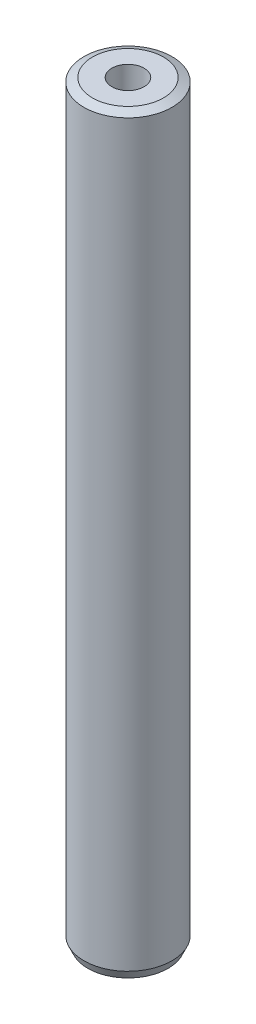
SolidWorks part; units mm, degrees
ref_plane "Front Plane" through (0, 0, 0) normal (0, 0, 1) x (1, 0, 0)
ref_plane "Top Plane" through (0, 0, 0) normal (0, 1, 0) x (1, 0, 0)
ref_plane "Right Plane" through (0, 0, 0) normal (1, 0, 0) x (0, 0, -1)
sketch "Sketch1" plane through (0, 0, 0) normal (0, 1, 0) x (1, 0, 0)
  circle A0 centre (0, 0) radius 15
  dimension "SHAFT_OD" = 30
extrude "Boss-Extrude1" add sketch "Sketch1" along normal blind 256.023
sketch "Sketch2" plane through (0, 0, 0) normal (0, 1, 0) x (1, 0, 0)
  circle A0 centre (0, 0) radius 5.493
  dimension "BORE_D" = 10.986
extrude "Cut-Extrude1" cut sketch "Sketch2" along normal through all
chamfer "Chamfer1" distance 1.3207 angle 65.616 2 edges at (0, 256.023, 15) (0, 0, 15) first distance on face at (0, 256.023, 15) first distance on face at (0, 0, 5.493)
